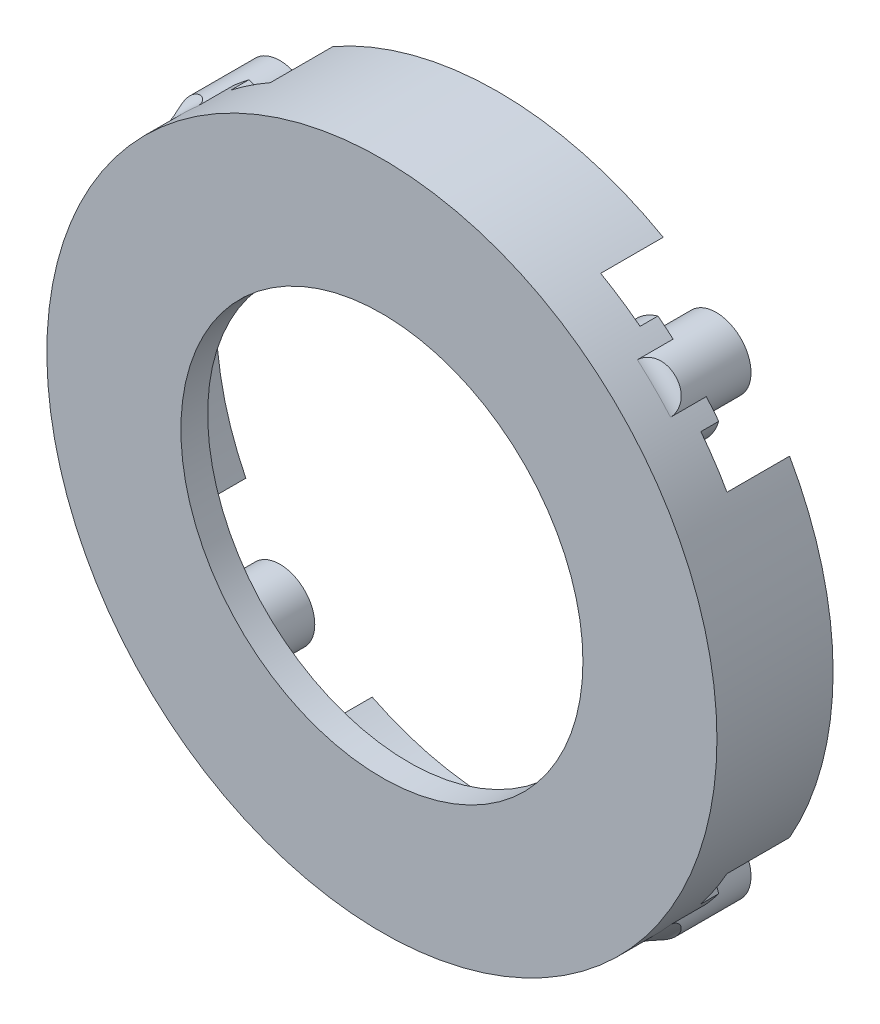
SolidWorks part; units mm, degrees
ref_plane "Front Plane" through (0, 0, 0) normal (0, 0, 1) x (1, 0, 0)
ref_plane "Top Plane" through (0, 0, 0) normal (0, 1, 0) x (1, 0, 0)
ref_plane "Right Plane" through (0, 0, 0) normal (1, 0, 0) x (0, 0, -1)
sketch "Sketch1" plane through (0, 0, 0) normal (0, 0, 1) x (1, 0, 0)
  circle A0 centre (0, 0) radius 31.55
  circle A1 centre (0, 0) radius 37.5
  dimension "D1" = 63.1
  dimension "D2" = 75
extrude "Boss-Extrude3" add sketch "Sketch1" along normal blind 13
sketch "Sketch3" plane through (0, 0, 13) normal (0, 0, 1) x (1, 0, 0)
  circle A0 centre (0, 0) radius 31.55
  circle A1 centre (0, 0) radius 22.5
  dimension "D1" = 45
extrude "Boss-Extrude4" add sketch "Sketch3" against normal blind 3
sketch "Sketch4" plane through (0, 0, 0) normal (0, 0, -1) x (-1, 0, 0)
  line L0 (14.0426, 28.1847) -> (18.4852, 32.6274)
  line L1 (28.1847, 14.0426) -> (32.6274, 18.4852)
  line L2 (0, 0) -> (0, 31.4893) construction
  line L3 (-28.1847, 14.0426) -> (-32.6274, 18.4852)
  line L4 (-14.0426, 28.1847) -> (-18.4852, 32.6274)
  line L5 (28.1847, -14.0426) -> (32.6274, -18.4852)
  line L6 (14.0426, -28.1847) -> (18.4852, -32.6274)
  line L7 (-14.0426, -28.1847) -> (-18.4852, -32.6274)
  line L8 (-28.1847, -14.0426) -> (-32.6274, -18.4852)
  arc A0 (-14.0426, 28.1847) -> (-28.1847, 14.0426) centre (0, 0) ccw
  circle A1 centre (0, 0) radius 37.5 construction
  arc A2 (-18.4852, 32.6274) -> (-32.6274, 18.4852) centre (0, 0) ccw
  arc A3 (28.1847, 14.0426) -> (14.0426, 28.1847) centre (0, 0) ccw
  arc A4 (32.6274, 18.4852) -> (18.4852, 32.6274) centre (0, 0) ccw
  arc A5 (14.0426, -28.1847) -> (28.1847, -14.0426) centre (0, 0) ccw
  arc A6 (18.4852, -32.6274) -> (32.6274, -18.4852) centre (0, 0) ccw
  arc A7 (-28.1847, -14.0426) -> (-14.0426, -28.1847) centre (0, 0) ccw
  arc A8 (-32.6274, -18.4852) -> (-18.4852, -32.6274) centre (0, 0) ccw
  point P24 (0, 0)
  dimension "D1" = 4
  dimension "D2" = 20
extrude "Cut-Extrude1" cut sketch "Sketch4" against normal blind 7
sketch "Sketch5" plane through (0, 0, 7) normal (0, 0, -1) x (-1, 0, 0)
  line L0 (-26.5165, 26.5165) -> (-22.3092, 22.3092) construction
  arc A0 (-18.4852, 32.6274) -> (-32.6274, 18.4852) centre (0, 0) ccw construction
  arc A1 (-14.0879, 28.23) -> (-28.23, 14.0879) centre (0, 0) ccw construction
  circle A2 centre (-24.4129, 24.4129) radius 3.9
  circle A3 centre (24.4129, 24.4129) radius 3.9
  circle A4 centre (24.4129, -24.4129) radius 3.9
  circle A5 centre (-24.4129, -24.4129) radius 3.9
  point P19 (0, 0)
  dimension "D1" = 7.8
  dimension "D2" = 4
extrude "Boss-Extrude5" add sketch "Sketch5" along normal blind 7
fillet "Fillet1" radius 2 8 edges at (22.3092, -22.3092, 7) (-22.3092, -22.3092, 7) (-22.3092, 22.3092, 7) (22.3092, 22.3092, 7) (-26.5165, 26.5165, 7) (-26.5165, -26.5165, 7) (26.5165, -26.5165, 7) (26.5165, 26.5165, 7)
sketch "Sketch6" plane through (0, 0, 7) normal (0, 0, -1) x (-1, 0, 0)
  arc A0 (-18.9708, 25.2093) -> (-22.8954, 29.6994) centre (-24.4129, 24.4129) ccw
  arc A1 (-22.8954, 29.6994) -> (-29.6994, 22.8954) centre (0, 0) ccw
  arc A2 (-18.9708, 25.2093) -> (-25.2093, 18.9708) centre (0, 0) ccw
  arc A3 (-29.6994, 22.8954) -> (-25.2093, 18.9708) centre (-24.4129, 24.4129) ccw
  arc A4 (25.2093, 18.9708) -> (29.6994, 22.8954) centre (24.4129, 24.4129) ccw
  arc A5 (29.6994, 22.8954) -> (22.8954, 29.6994) centre (0, 0) ccw
  arc A6 (22.8954, 29.6994) -> (18.9708, 25.2093) centre (24.4129, 24.4129) ccw
  arc A7 (25.2093, 18.9708) -> (18.9708, 25.2093) centre (0, 0) ccw
  arc A8 (18.9708, -25.2093) -> (22.8954, -29.6994) centre (24.4129, -24.4129) ccw
  arc A9 (22.8954, -29.6994) -> (29.6994, -22.8954) centre (0, 0) ccw
  arc A10 (29.6994, -22.8954) -> (25.2093, -18.9708) centre (24.4129, -24.4129) ccw
  arc A11 (18.9708, -25.2093) -> (25.2093, -18.9708) centre (0, 0) ccw
  arc A12 (-25.2093, -18.9708) -> (-29.6994, -22.8954) centre (-24.4129, -24.4129) ccw
  arc A13 (-29.6994, -22.8954) -> (-22.8954, -29.6994) centre (0, 0) ccw
  arc A14 (-22.8954, -29.6994) -> (-18.9708, -25.2093) centre (-24.4129, -24.4129) ccw
  arc A15 (-25.2093, -18.9708) -> (-18.9708, -25.2093) centre (0, 0) ccw
  point P26 (0, 0)
  dimension "D1" = 11
  dimension "D2" = 4
extrude "Boss-Extrude6" add sketch "Sketch6" along normal blind 2
